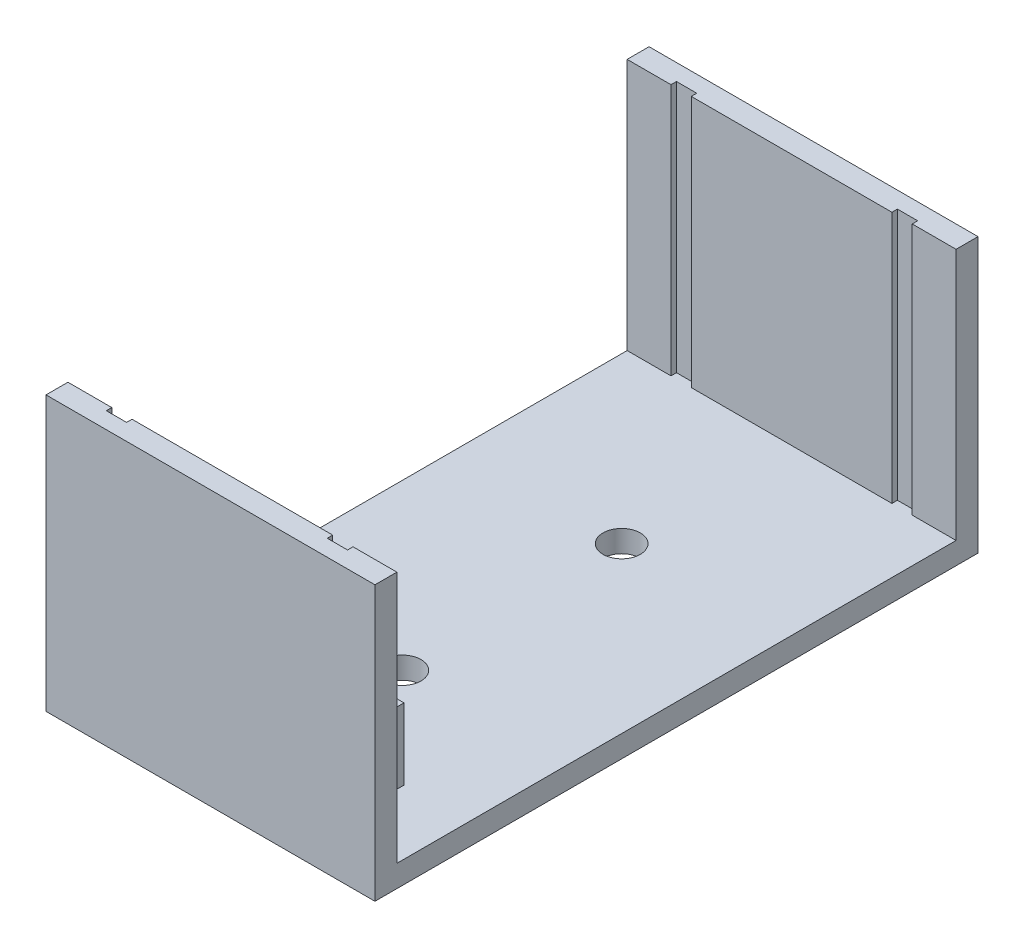
SolidWorks part; units mm, degrees
ref_plane "Front Plane" through (0, 0, 0) normal (0, 0, 1) x (1, 0, 0)
ref_plane "Top Plane" through (0, 0, 0) normal (0, 1, 0) x (1, 0, 0)
ref_plane "Right Plane" through (0, 0, 0) normal (1, 0, 0) x (0, 0, -1)
sketch "Sketch1" plane through (0, 0, 0) normal (0, 1, 0) x (1, 0, 0)
  line L0 (0, 27.5) -> (0, -27.5) construction
  line L1 (-15, 27.5) -> (15, 27.5)
  line L2 (-15, 27.5) -> (-15, -27.5)
  line L3 (-15, -27.5) -> (15, -27.5)
  line L4 (15, 27.5) -> (15, -27.5)
  line L5 (-15, 27.5) -> (15, -27.5) construction
  line L6 (-15, -27.5) -> (15, 27.5) construction
  line L7 (15, 0) -> (-15, 0) construction
  line L8 (-15, 25.5) -> (-11, 25.5)
  line L9 (-11, 25.5) -> (-11, 26)
  line L10 (-11, 26) -> (-9.15, 26)
  line L11 (-9.15, 26) -> (-9.15, 25.5)
  line L12 (-9.15, 25.5) -> (9.15, 25.5)
  line L13 (11, 25.5) -> (11, 26)
  line L14 (9.15, 26) -> (9.15, 25.5)
  line L15 (11, 26) -> (9.15, 26)
  line L16 (-15, 27.5) -> (-15, -27.5)
  line L17 (15, 27.5) -> (15, -27.5)
  line L18 (15, 25.5) -> (11, 25.5)
  line L19 (-15, -25.5) -> (-11, -25.5)
  line L20 (-11, -25.5) -> (-11, -26)
  line L21 (-11, -26) -> (-9.15, -26)
  line L22 (-9.15, -26) -> (-9.15, -25.5)
  line L23 (15, -25.5) -> (11, -25.5)
  line L24 (11, -25.5) -> (11, -26)
  line L25 (11, -26) -> (9.15, -26)
  line L26 (-9.15, -25.5) -> (9.15, -25.5)
  line L27 (9.15, -26) -> (9.15, -25.5)
  point P0 (0, 0)
  point P20 (0, 25.5)
  dimension "D1" = 30
  dimension "D2" = 55
  dimension "D3" = 26
  dimension "D4" = 0.5
  dimension "D5" = 0.5
  dimension "D6" = 1.85
  dimension "D7" = 4
extrude "Boss-Extrude1" add sketch "Sketch1" along normal blind 25 contours L25 L27 L26 L22 L21 L20 L19 L16 L3 L4 L23 L24 | L18 L4 L1 L2 L8 L9 L10 L11 L12 L14 L15 L13 region at (0, 0, -26.5239) region at (0, 0, 26.5239)
extrude "Boss-Extrude2" add sketch "Sketch1<3>" along normal blind 2 contours L27 L25 L24 L23 L17 L18 L13 L15 L14 L12 L11 L10 L9 L8 L2 L19 L20 L21 L22 L26 region at (0, 0, 0)
sketch "Sketch1<3>" plane through (0, 0, 0) normal (0, 1, 0) x (1, 0, 0) same geometry as "Sketch1"
sketch "Sketch2" plane through (0, 2, 0) normal (0, 1, 0) x (1, 0, 0)
  line L0 (0, 25.5) -> (0, -25.5) construction
  line L1 (9.15, -26) -> (9.15, -25.5) construction
  line L3 (-9.15, 25.5) -> (9.15, 25.5) construction
  line L4 (-9.15, -25.5) -> (9.15, -25.5) construction
  line L6 (-9.15, -25.5) -> (9.15, -25.5)
  line L7 (-9.15, -25.5) -> (-9.15, -19)
  line L8 (-9.15, -19) -> (9.15, -19)
  line L9 (9.15, -25.5) -> (9.15, -19)
  dimension "D1" = 6.5
extrude "Boss-Extrude3" add sketch "Sketch2" along normal blind 6.5
sketch "Sketch3" plane through (9.15, 0, 0) normal (1, 0, 0) x (0, 0, -1)
  line L0 (-19, 8.5) -> (-25.5, 8.5) construction
  line L1 (-25.5, 8.5) -> (-25.5, 2) construction
  line L2 (-25.5, 2) -> (-19, 2) construction
  line L3 (-26, 25) -> (-26, 2) construction
  circle A0 centre (-21.7, 5.8) radius 1.45
  dimension "D3" = 2.9
  dimension "D1" = 3.8
  dimension "D2" = 4.3
extrude "Cut-Extrude1" cut sketch "Sketch3" against normal up to next
sketch "Sketch4" plane through (0, 2, 0) normal (0, 1, 0) x (1, 0, 0)
  line L0 (0, -19) -> (0, 25.5) construction
  line L1 (9.15, -19) -> (-9.15, -19) construction
  line L2 (-9.15, 25.5) -> (9.15, 25.5) construction
  line L4 (-2.875, 8.3401) -> (0, 6.6802)
  line L5 (0, 6.6802) -> (2.875, 8.3401)
  line L6 (2.875, 8.3401) -> (2.875, 11.6599)
  line L7 (2.875, 11.6599) -> (0, 13.3198)
  line L8 (0, 13.3198) -> (-2.875, 11.6599)
  line L9 (-2.875, 11.6599) -> (-2.875, 8.3401)
  line L10 (0, -13.3198) -> (2.875, -11.6599)
  line L11 (2.875, -11.6599) -> (2.875, -8.3401)
  line L12 (2.875, -8.3401) -> (0, -6.6802)
  line L13 (0, -6.6802) -> (-2.875, -8.3401)
  line L14 (-2.875, -8.3401) -> (-2.875, -11.6599)
  line L15 (-2.875, -11.6599) -> (0, -13.3198)
  line L17 (15, 0) -> (-15, 0) construction
  line L18 (15, 25.5) -> (15, -25.5) construction
  line L19 (-15, 25.5) -> (-15, -25.5) construction
  circle A0 centre (0, 10) radius 2.875 construction
  circle A1 centre (0, -10) radius 2.875 construction
  circle A4 centre (0, 10) radius 1.7
  circle A5 centre (0, -10) radius 1.7
  dimension "D3" = 5.75
  dimension "D4" = 5.75
  dimension "D5" = 3.4
  dimension "D1" = 10
  dimension "D2" = 10
extrude "Cut-Extrude3" cut sketch "Sketch4" against normal up to next contours A4 | A5 region at (0, 2, -10) region at (0, 2, 10)
